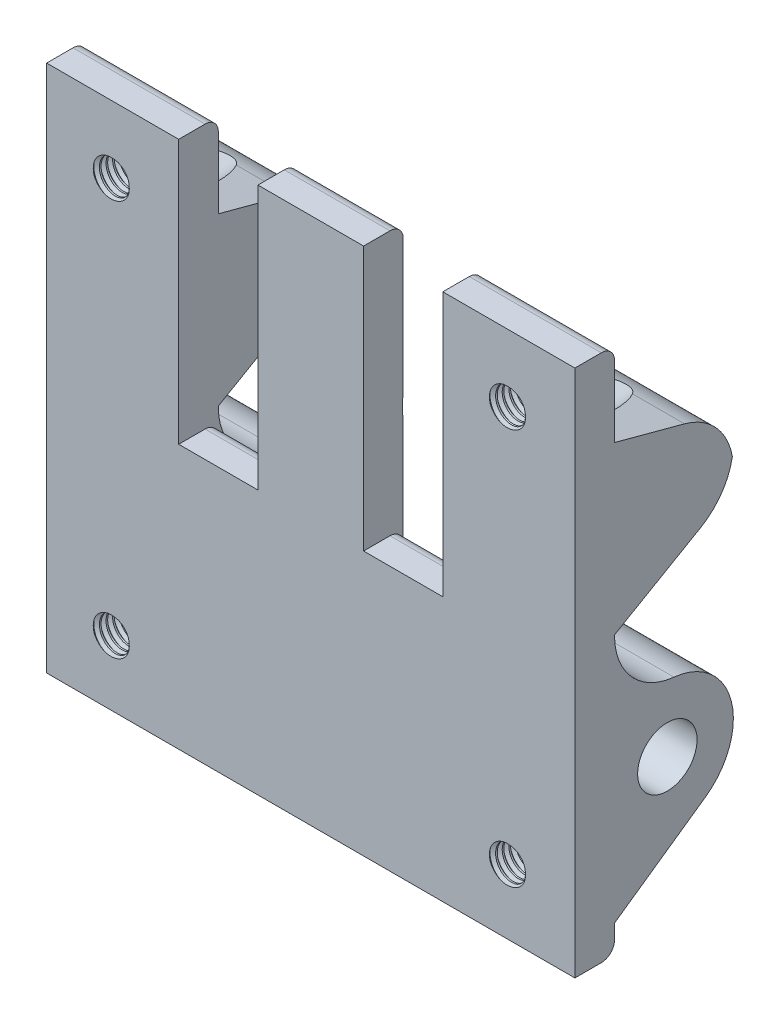
SolidWorks part; units mm, degrees
ref_plane "Front Plane" through (0, 0, 0) normal (0, 0, 1) x (1, 0, 0)
ref_plane "Top Plane" through (0, 0, 0) normal (0, 1, 0) x (1, 0, 0)
ref_plane "Right Plane" through (0, 0, 0) normal (1, 0, 0) x (0, 0, -1)
sketch "Sketch2" plane through (0, 0, 0) normal (1, 0, 0) x (0, 0, -1)
  line L3 (7, 16.0053) -> (3, 16.0053)
  line L4 (3, 16.0053) -> (3, 21.0053)
  line L6 (12, 26.2015) -> (12, 31.2015)
  line L7 (12, 31.2015) -> (3, 33.613)
  line L8 (0, 16.0053) -> (0, 0)
  line L9 (0, 0) -> (9.8679, 6.9096) construction
  line L10 (12, 11.0053) -> (12, 26.2015) construction
  line L11 (3, 21.0053) -> (12, 26.2015)
  line L15 (0, 16.0053) -> (0, 40)
  line L16 (0, 40) -> (3, 40)
  line L17 (3, 40) -> (3, 33.613)
  line L18 (0, 0) -> (3, 0)
  line L19 (3, 0) -> (3, 2.1006)
  line L20 (3, 2.1006) -> (9.8679, 6.9096)
  circle A1 centre (7, 11.0053) radius 2.25
  arc A3 (7, 16.0053) -> (9.8679, 6.9096) centre (7, 11.0053) cw
  point P2 (0, 0)
  point P3 (0, 0)
  dimension "D1" = 120
  dimension "D4" = 4.5
  dimension "D5" = 5
  dimension "D2" = 4
  dimension "D3" = 75
  dimension "D7" = 3
  dimension "D8" = 55
  dimension "D9" = 5
  dimension "D10" = 5
  dimension "D11" = 40
extrude "Boss-Extrude2" add sketch "Sketch2" along normal mid plane 40
sketch "Sketch3" plane through (0, 0, 0) normal (0, 1, 0) x (1, 0, 0)
  line L0 (0, 12) -> (0, 0) construction
  line L1 (20, 12) -> (-20, 12) construction
  line L2 (20, 0) -> (-20, 0) construction
  line L3 (20, 3) -> (-20, 3) construction
  line L4 (-10, 3) -> (10, 3)
  line L5 (-10, 3) -> (-10, 12)
  line L6 (-10, 12) -> (10, 12)
  line L7 (10, 3) -> (10, 12)
  line L8 (0, 12) -> (0, 3) construction
  line L9 (-10, 7.5) -> (10, 7.5) construction
  point P6 (0, 7.5)
  dimension "D1" = 20
extrude "Hinge Cutout" cut sketch "Sketch3" along normal through all both and the other way through all
hole_wizard "Tap Drill for M3x0.5 Tap1" positions "Sketch8" profile "Sketch7" hole size "M3x0.5" standard "ANSI Metric"
sketch "Sketch8" plane through (0, 0, -3) normal (0, 0, -1) x (-1, 0, 0)
  line L3 (0, 20) -> (-20, 20) construction
  line L4 (-20, 21.0053) -> (-20, 26.2015) construction
  line L8 (0, 0) -> (0, 40) construction
  line L10 (-20, 40) -> (20, 40) construction
  line L12 (-20, 0) -> (20, 0) construction
  point P0 (-15, 35)
  point P19 (-15, 5)
  point P41 (0, 20)
  point P44 (15, 5)
  point P45 (15, 35)
  dimension "D1" = 30
  dimension "D2" = 30
sketch "Sketch7" plane through (15, 35, -3) normal (1, 0, 0) x (0, 1, 0)
  line L0 (0, 0) -> (0, 3)
  line L1 (0, 3) -> (1.25, 3)
  line L2 (1.25, 3) -> (1.25, 0)
  line L5 (1.25, 0) -> (0, 0)
  line L11 (0, -6.35) -> (0, 107.95) construction
  dimension "Thru Hole Dia." = 2.5
  dimension "Thru Hole Depth" = 3
fillet "Fillet1" radius 5 6 edges at (-15, 16.0053, -3) (15, 16.0053, -3) (-15, 26.2015, -12) (15, 26.2015, -12) (-15, 31.2015, -12) (15, 31.2015, -12)
sketch "Sketch15" plane through (0, 0, 0) normal (1, 0, 0) x (0, 0, -1)
  line L0 (0, 40) -> (0, 0) construction
  line L1 (7, 11.0053) -> (9.1752, 28.8734) construction
  line L2 (2.75, 28.4964) -> (7, 11.0053) construction
  line L3 (3, 40) -> (0, 40) construction
  line L4 (1.5, 28.4964) -> (1.5, 40) construction
  line L6 (10.4252, 28.8734) -> (10.4252, 40) construction
  arc A0 (2.75, 28.4964) -> (9.1752, 28.8734) centre (7, 11.0053) cw construction
  arc A1 (9.3262, 30.1143) -> (2.4549, 29.7111) centre (7, 11.0053) ccw
  arc A2 (3.0451, 27.2817) -> (9.0241, 27.6326) centre (7, 11.0053) cw
  arc A3 (9.3262, 30.1143) -> (9.0241, 27.6326) centre (9.1752, 28.8734) cw
  arc A4 (2.4549, 29.7111) -> (3.0451, 27.2817) centre (2.75, 28.4964) ccw
  dimension "D3" = 18
  dimension "D4" = 2.5
  dimension "D1" = 1.5
  dimension "D2" = 1.5
extrude "Arc Slot" [suppressed] cut sketch "Sketch15" along normal through all both and the other way through all
sketch "Sketch14" plane through (0, 0, -3) normal (0, 0, -1) x (-1, 0, 0)
  line L0 (0, 40) -> (0, 0) construction
  line L1 (-20, 40) -> (20, 40) construction
  line L2 (-20, 0) -> (20, 0) construction
  line L3 (-10, 28.2265) -> (-10, 32.1945) construction
  line L4 (-10, 40) -> (-4, 40)
  line L5 (-10, 40) -> (-10, 20)
  line L6 (-10, 20) -> (-4, 20)
  line L7 (-4, 40) -> (-4, 20)
  line L8 (10, 20) -> (4, 20)
  line L9 (4, 40) -> (4, 20)
  line L10 (10, 40) -> (4, 40)
  line L11 (10, 40) -> (10, 20)
  dimension "D1" = 6
  dimension "D2" = 20
extrude "Hinge Teeth cutout" cut sketch "Sketch14" against normal through all
sketch "Sketch16" plane through (0, 0, 0) normal (1, 0, 0) x (0, 0, -1)
  line L1 (0, 40) -> (3, 40)
  line L2 (0, 40) -> (0, 0)
  line L3 (0, 0) -> (3, 0)
  line L4 (3, 40) -> (3, 0)
extrude "Fill in for above" add sketch "Sketch16" along normal mid plane 8
sketch "Sketch13" plane through (0, 0, -3) normal (0, 0, -1) x (-1, 0, 0)
  line L0 (0, 40) -> (0, 0) construction
  line L2 (-20, 0) -> (20, 0) construction
  line L3 (-10, 40) -> (10, 40) construction
  line L6 (-4, 40) -> (4, 40) construction
  line L7 (-20, 40) -> (-10, 40) construction
  line L8 (-20, 0) -> (20, 0) construction
  circle A0 centre (0, 28) radius 2.413
  circle A1 centre (0, 28) radius 3.302
  dimension "D1" = 6.604
  dimension "D2" = 4.826
  dimension "D3" = 28
extrude "Spring Cutout" cut sketch "Sketch13" against normal blind 2
sketch "Sketch17" plane through (0, 0, -3) normal (0, 0, -1) x (-1, 0, 0)
  circle A0 centre (-15, 35) radius 3
  circle A1 centre (-15, 35) radius 1.25 construction
  circle A2 centre (-15, 5) radius 3
  circle A3 centre (15, 5) radius 3
  circle A4 centre (15, 35) radius 3
  circle A5 centre (15, 35) radius 1.25 construction
  circle A6 centre (-15, 5) radius 1.25 construction
  circle A7 centre (15, 5) radius 1.25 construction
  dimension "D1" = 6
extrude "Cut-Extrude10" cut sketch "Sketch17" along normal through all
fillet "Fillet2" radius 1 2 edges at (0, 31.302, -3) (0, 30.413, -3)
fillet "Fillet3" radius 1 6 edges at (0, 40, -3) (-15, 40, -3) (7, 20, -3) (-7, 20, -3) (15, 40, -3) (0, 0, -3)
thread "Thread1" pitch 0.5 start angle 0, offset 0, length 10, pitch 0.5, diameter 2.5
ref_plane "Plane1" through (16.25, 5, -3) normal (0, -1, 0) x (1, 0, 0)
sketch "Thread Profile1" plane through (16.25, 5, -3) normal (0, -1, 0) x (1, 0, 0)
  line L0 (0, 0) -> (0, 0.5) construction
  line L1 (0, 0) -> (0.2706, 0.1562)
  line L2 (0.2706, 0.1562) -> (0.2706, 0.2187)
  line L3 (0.2706, 0.2187) -> (0, 0.375)
  line L4 (0.2706, 0.1875) -> (0, 0.1875) construction
  line L11 (0, 0) -> (0, 0.375)
  point P2 (0, 0)
  dimension "Pitch" = 0.5
  dimension "Profile_Angle" = 60
  dimension "Profile_Land" = 0.0625
  dimension "Profile_Height" = 0.2706
thread "Thread2" pitch 0.5 profile "Thread Profile2" start angle 0, offset 0, length 10, pitch 0.5, diameter 2.5
ref_plane "Plane2" through (-13.75, 5, -3) normal (0, -1, 0) x (1, 0, 0)
sketch "Thread Profile2" plane through (-13.75, 5, -3) normal (0, -1, 0) x (1, 0, 0)
  line L0 (0, 0) -> (0, 0.5) construction
  line L1 (0, 0) -> (0.2706, 0.1562)
  line L2 (0.2706, 0.1562) -> (0.2706, 0.2187)
  line L3 (0.2706, 0.2187) -> (0, 0.375)
  line L4 (0.2706, 0.1875) -> (0, 0.1875) construction
  line L11 (0, 0) -> (0, 0.375)
  point P2 (0, 0)
  dimension "Pitch" = 0.5
  dimension "Profile_Angle" = 60
  dimension "Profile_Land" = 0.0625
  dimension "Profile_Height" = 0.2706
thread "Thread3" pitch 0.5 profile "Thread Profile3" start angle 0, offset 0, length 10, pitch 0.5, diameter 2.5
ref_plane "Plane3" through (-13.75, 35, -3) normal (0, -1, 0) x (1, 0, 0)
sketch "Thread Profile3" plane through (-13.75, 35, -3) normal (0, -1, 0) x (1, 0, 0)
  line L0 (0, 0) -> (0, 0.5) construction
  line L1 (0, 0) -> (0.2706, 0.1562)
  line L2 (0.2706, 0.1562) -> (0.2706, 0.2187)
  line L3 (0.2706, 0.2187) -> (0, 0.375)
  line L4 (0.2706, 0.1875) -> (0, 0.1875) construction
  line L11 (0, 0) -> (0, 0.375)
  point P2 (0, 0)
  dimension "Pitch" = 0.5
  dimension "Profile_Angle" = 60
  dimension "Profile_Land" = 0.0625
  dimension "Profile_Height" = 0.2706
thread "Thread4" pitch 0.5 profile "Thread Profile4" start angle 0, offset 0, length 10, pitch 0.5, diameter 2.5
ref_plane "Plane4" through (16.25, 35, -3) normal (0, -1, 0) x (1, 0, 0)
sketch "Thread Profile4" plane through (16.25, 35, -3) normal (0, -1, 0) x (1, 0, 0)
  line L0 (0, 0) -> (0, 0.5) construction
  line L1 (0, 0) -> (0.2706, 0.1562)
  line L2 (0.2706, 0.1562) -> (0.2706, 0.2187)
  line L3 (0.2706, 0.2187) -> (0, 0.375)
  line L4 (0.2706, 0.1875) -> (0, 0.1875) construction
  line L11 (0, 0) -> (0, 0.375)
  point P2 (0, 0)
  dimension "Pitch" = 0.5
  dimension "Profile_Angle" = 60
  dimension "Profile_Land" = 0.0625
  dimension "Profile_Height" = 0.2706
